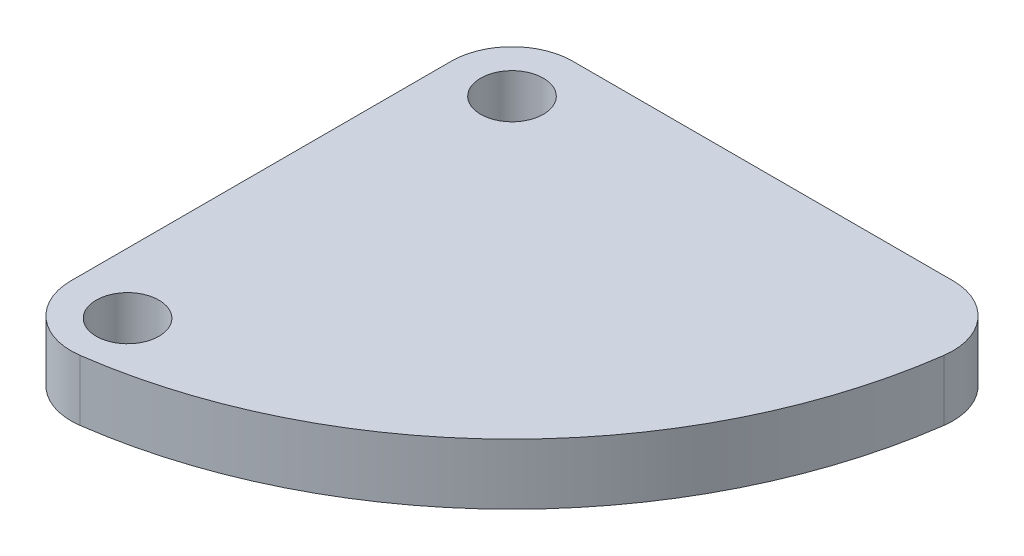
SolidWorks part; units mm, degrees
ref_plane "Front Plane" through (0, 0, 0) normal (0, 0, 1) x (1, 0, 0)
ref_plane "Top Plane" through (0, 0, 0) normal (0, 1, 0) x (1, 0, 0)
ref_plane "Right Plane" through (0, 0, 0) normal (1, 0, 0) x (0, 0, -1)
sketch "Sketch1" plane through (0, 0, 0) normal (0, 1, 0) x (1, 0, 0)
  line L1 (-12.5, -12.5) -> (12.5, -12.5)
  line L2 (-12.5, -12.5) -> (-12.5, 12.5)
  line L3 (-12.5, 12.5) -> (12.5, 12.5)
  line L4 (12.5, -12.5) -> (12.5, 12.5)
  line L5 (-12.5, -12.5) -> (12.5, 12.5) construction
  line L6 (-12.5, 12.5) -> (12.5, -12.5) construction
  circle A0 centre (-9.5, 9.5) radius 1.55
  circle A1 centre (-9.5, -9.5) radius 1.55
  point P0 (0, 0)
  dimension "D3" = 3.1
  dimension "D1" = 25
  dimension "D2" = 25
  dimension "D4" = 3
  dimension "D5" = 2
extrude "Boss-Extrude1" add sketch "Sketch1" against normal blind 3
fillet "Fillet1" radius 25 1 edges at (12.5, -1.5, 12.5)
fillet "Fillet2" radius 3 3 edges at (12.5, -1.5, -12.5) (-12.5, -1.5, 12.5) (-12.5, -1.5, -12.5)
